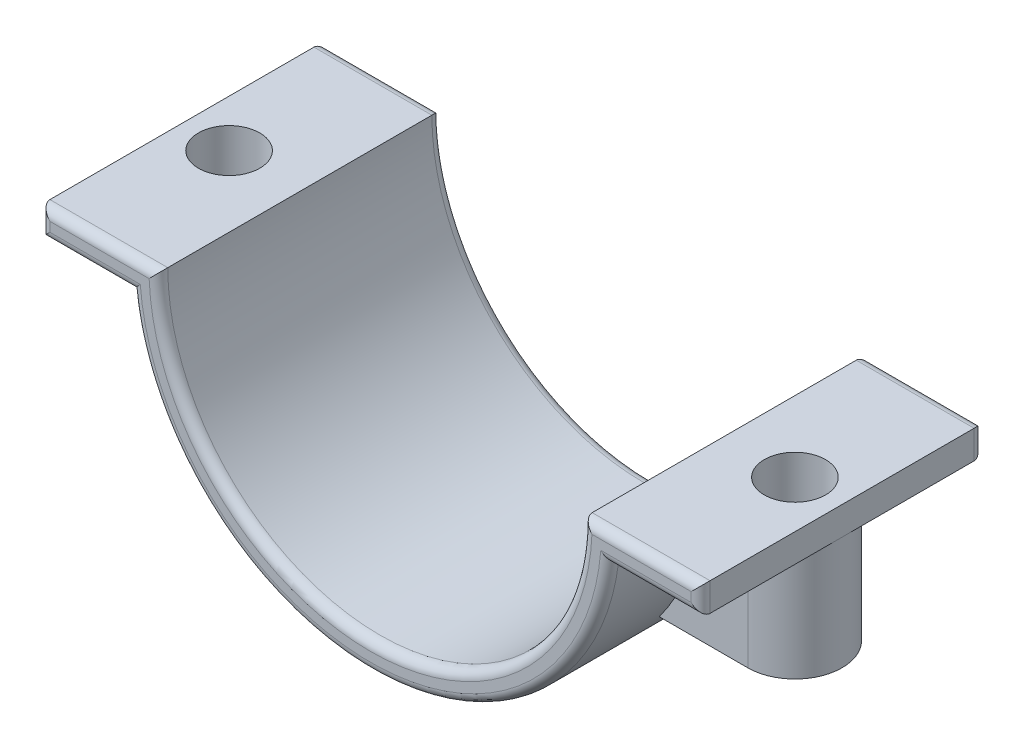
SolidWorks part; units mm, degrees
ref_plane "Front Plane" through (0, 0, 0) normal (0, 0, 1) x (1, 0, 0)
ref_plane "Top Plane" through (0, 0, 0) normal (0, 1, 0) x (1, 0, 0)
ref_plane "Right Plane" through (0, 0, 0) normal (1, 0, 0) x (0, 0, -1)
sketch "Sketch1" plane through (0, 0, 0) normal (0, 0, 1) x (1, 0, 0)
  line L0 (-35, 0) -> (-22.5, 0)
  line L1 (22.5, 0) -> (35, 0)
  line L2 (-35, -3) -> (-25.3229, -3)
  line L3 (25.3229, -3) -> (35, -3)
  line L4 (-35, 0) -> (-35, -3)
  line L5 (35, 0) -> (35, -3)
  arc A0 (-22.5, 0) -> (22.5, 0) centre (0, 0) ccw
  arc A1 (-25.3229, -3) -> (25.3229, -3) centre (0, 0) ccw
  point P6 (0, 0)
  dimension "D1" = 22.5
  dimension "D2" = 35
  dimension "D3" = 3
extrude "Boss-Extrude1" add sketch "Sketch1" along normal mid plane 30
sketch "Sketch4" plane through (0, -3, 0) normal (0, -1, 0) x (1, 0, 0)
  line L0 (25.3229, 15) -> (25.3229, -15) construction
  line L1 (20.6458, 5) -> (30, 5)
  line L2 (20.6458, 5) -> (20.6458, -5)
  line L3 (20.6458, -5) -> (30, -5)
  line L4 (30, 5) -> (30, -5)
  line L5 (20.6458, 5) -> (30, -5) construction
  line L6 (20.6458, -5) -> (30, 5) construction
  line L7 (35, 15) -> (35, -15) construction
  circle A0 centre (30, 0) radius 5
  circle A1 centre (30, 0) radius 3.25
  point P0 (25.3229, 0)
  line M9 (25.3229, 15) -> (25.3229, -15)
  dimension "D1" = 10
  dimension "D2" = 6.5
extrude "Boss-Extrude5" add sketch "Sketch4" against normal up to body from offset 12 contours A1 L4 A0 | A1 L4 A0 M9 | L4 A1 | L4 A1 | L1 L4 L3 L2 region at (33.4565, -3, 3.4565) region at (29.8896, -3, 4.125) region at (31.3793, -3, 0) region at (28.6207, -3, 0)
extrude "Cut-Extrude1" cut sketch "Sketch4<5>" against normal through all both and the other way through all contours L4 A1 | L4 A1 region at (31.3793, -3, 0) region at (28.6207, -3, 0)
sketch "Sketch4<5>" plane through (0, -3, 0) normal (0, -1, 0) x (1, 0, 0) same geometry as "Sketch4"
mirror "Mirror1" about plane through (0, 0, 0) normal (1, 0, 0) of "Boss-Extrude5", "Cut-Extrude1"
fillet "Fillet1" radius 1 16 edges at (28.75, 0, 15) (35, -1.5, 15) (30.1615, -3, 15) (0, -25.5, 15) (-30.1615, -3, 15) (-35, -1.5, 15) (-28.75, 0, 15) (0, -22.5, 15) (-28.75, 0, -15) (-35, -1.5, -15) (-30.1615, -3, -15) (0, -25.5, -15) (30.1615, -3, -15) (35, -1.5, -15) (28.75, 0, -15) (0, -22.5, -15)
